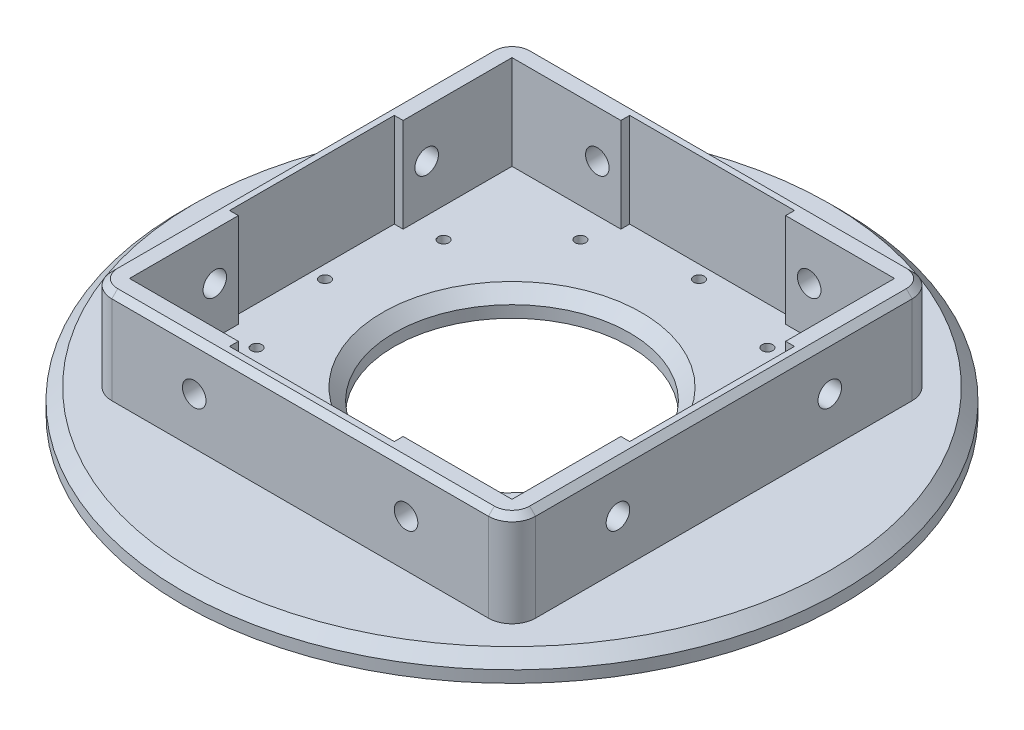
SolidWorks part; units mm, degrees
material "6061-T6 (SS)"
ref_plane "Front Plane" through (0, 0, 0) normal (0, 0, 1) x (1, 0, 0)
ref_plane "Top Plane" through (0, 0, 0) normal (0, 1, 0) x (1, 0, 0)
ref_plane "Right Plane" through (0, 0, 0) normal (1, 0, 0) x (0, 0, -1)
sketch "Sketch1" plane through (0, 0, 0) normal (0, 1, 0) x (1, 0, 0)
  line L0 (-57.15, 57.15) -> (57.15, 57.15)
  line L1 (-22.225, -53.975) -> (22.225, -53.975)
  line L2 (-53.975, -22.225) -> (-53.975, 22.225)
  line L3 (-22.225, 53.975) -> (22.225, 53.975)
  line L4 (53.975, -22.225) -> (53.975, 22.225)
  line L5 (-53.975, -53.975) -> (53.975, 53.975) construction
  line L6 (-53.975, 53.975) -> (53.975, -53.975) construction
  line L7 (57.15, -57.15) -> (57.15, 57.15)
  line L8 (-57.15, -57.15) -> (57.15, -57.15)
  line L9 (-57.15, -57.15) -> (-57.15, 57.15)
  line L10 (-22.225, 53.975) -> (-22.225, 51.5938)
  line L11 (-51.5937, -51.5938) -> (-22.225, -51.5938)
  line L12 (-51.5937, -51.5938) -> (-51.5938, -22.225)
  line L13 (-51.5937, 51.5938) -> (-22.225, 51.5938)
  line L14 (51.5938, -51.5938) -> (51.5937, -22.225)
  line L15 (-51.5937, -51.5938) -> (51.5938, 51.5938) construction
  line L16 (-51.5937, 51.5938) -> (51.5938, -51.5938) construction
  line L17 (-53.975, 22.225) -> (-51.5938, 22.225)
  line L18 (22.225, 53.975) -> (22.225, 51.5938)
  line L19 (53.975, 22.225) -> (51.5937, 22.225)
  line L20 (-53.975, -22.225) -> (-51.5938, -22.225)
  line L21 (-22.225, -53.975) -> (-22.225, -51.5938)
  line L22 (22.225, -53.975) -> (22.225, -51.5938)
  line L23 (53.975, -22.225) -> (51.5937, -22.225)
  line L24 (-51.5938, 22.225) -> (-51.5937, 51.5938)
  line L25 (-53.975, 53.975) -> (53.975, 53.975) construction
  line L26 (-53.975, -53.975) -> (-53.975, 53.975) construction
  line L27 (22.225, -51.5938) -> (51.5938, -51.5938)
  line L28 (53.975, -53.975) -> (53.975, 53.975) construction
  line L29 (51.5937, 22.225) -> (51.5938, 51.5938)
  line L30 (22.225, 51.5938) -> (51.5938, 51.5938)
  line L31 (-53.975, -53.975) -> (53.975, -53.975) construction
  circle A0 centre (0, 0) radius 88.9
  circle A1 centre (0, 0) radius 50.4444 construction
  circle A2 centre (0, 50.4444) radius 1.4351
  circle A14 centre (0, 0) radius 31.75
  circle A15 centre (25.2222, 43.6861) radius 1.4351
  circle A16 centre (43.6861, 25.2222) radius 1.4351
  circle A17 centre (50.4444, 0) radius 1.4351
  circle A18 centre (43.6861, -25.2222) radius 1.4351
  circle A19 centre (25.2222, -43.6861) radius 1.4351
  circle A20 centre (0, -50.4444) radius 1.4351
  circle A21 centre (-25.2222, -43.6861) radius 1.4351
  circle A22 centre (-43.6861, -25.2222) radius 1.4351
  circle A23 centre (-50.4444, 0) radius 1.4351
  circle A24 centre (-43.6861, 25.2222) radius 1.4351
  circle A25 centre (-25.2222, 43.6861) radius 1.4351
  point P30 (10.7306, 18.5859)
  point P58 (-53.975, 0)
  point P59 (53.975, 0)
  point P60 (0, 53.975)
  point P61 (0, -53.975)
  point P64 (0, 0)
  dimension "D1" = 177.8
  dimension "D2" = 2.8702
  dimension "D3" = 100.8888
  dimension "D9" = 63.5
  dimension "D5" = 107.95
  dimension "D6" = 107.95
  dimension "D8" = 103.1875
  dimension "D10" = 44.45
  dimension "D11" = 44.45
  dimension "D12" = 103.1875
  dimension "D7" = 3.175
  dimension "D4" = 12
extrude "Boss-Extrude1" add sketch "Sketch1" along normal blind 6.35 contours A0 L8 L9 L0 L7 | L30 L18 L3 L10 L13 L24 L17 L2 L20 L12 L11 L21 L1 L22 L27 L14 L23 L4 L19 L29 A14 A24 A23 A22 A21 A20 A19 A18 A17 A16 A15 A2 region at (-20.6984, 0, 52.7844) region at (-86.3855, 0, 0)
extrude "Boss-Extrude2" add sketch "Sketch1<3>" along normal blind 31.75 contours L9 L8 L7 L0 L18 L30 L29 L19 L4 L23 L14 L27 L22 L1 L21 L11 L12 L20 L2 L17 L24 L13 L10 L3 region at (0, 0, -55.5336)
sketch "Sketch1<3>" plane through (0, 0, 0) normal (0, 1, 0) x (1, 0, 0) same geometry as "Sketch1"
sketch "Sketch3" plane through (0, 0, 0) normal (0, 0, 1) x (1, 0, 0)
  line L0 (0, 31.75) -> (0, 6.35) construction
  line L1 (-57.15, 19.05) -> (57.15, 19.05) construction
  line L4 (-57.15, 6.35) -> (57.15, 6.35)
  line L5 (57.15, 6.35) -> (57.15, 31.75)
  line L6 (57.15, 31.75) -> (-57.15, 31.75)
  line L7 (-57.15, 31.75) -> (-57.15, 6.35)
  line L8 (-57.15, 6.35) -> (57.15, 6.35) construction
  line L9 (57.15, 6.35) -> (57.15, 31.75) construction
  line L10 (57.15, 31.75) -> (-57.15, 31.75) construction
  line L11 (-57.15, 31.75) -> (-57.15, 6.35) construction
  circle A0 centre (-28.575, 19.05) radius 3.175
  circle A1 centre (28.575, 19.05) radius 3.175
  point P9 (0, 19.05)
  dimension "D2" = 28.575
  dimension "D4" = 6.35
  dimension "D3" = 28.575
  dimension "D1" = 0
extrude "Cut-Extrude1" cut sketch "Sketch3" against normal through all and the other way through all contours L1 A0 | A0 | A1 region at (-28.575, 19.05, 0)
sketch "Sketch4" plane through (0, 0, 0) normal (1, 0, 0) x (0, 0, -1)
  line L0 (0, 31.75) -> (0, 6.35) construction
  line L1 (-57.15, 19.05) -> (57.15, 19.05) construction
  line L2 (-57.15, 6.35) -> (57.15, 6.35) construction
  line L3 (57.15, 6.35) -> (57.15, 31.75) construction
  line L4 (57.15, 31.75) -> (-57.15, 31.75) construction
  line L5 (-57.15, 31.75) -> (-57.15, 6.35) construction
  line L6 (-57.15, 31.75) -> (57.15, 31.75) construction
  circle A0 centre (-28.575, 19.05) radius 3.175
  circle A1 centre (28.575, 19.05) radius 3.175
  point P9 (0, 19.05)
  dimension "D3" = 6.35
  dimension "D1" = 28.575
  dimension "D2" = 28.575
extrude "Cut-Extrude2" cut sketch "Sketch4" against normal through all both and the other way through all
fillet "Fillet1" radius 6.35 4 edges at (-57.15, 19.05, 57.15) (-57.15, 19.05, -57.15) (57.15, 19.05, -57.15) (57.15, 19.05, 57.15)
chamfer "Chamfer1" distance 3.175 angle 45 2 edges at (0, 6.35, 88.9) (0, 6.35, 31.75)
chamfer "Chamfer2" distance 1.5875 angle 45 8 edges at (0, 31.75, -57.15) (-55.2901, 31.75, -55.2901) (55.2901, 31.75, -55.2901) (-57.15, 31.75, 0) (57.15, 31.75, 0) (-55.2901, 31.75, 55.2901) (55.2901, 31.75, 55.2901) (0, 31.75, 57.15)
